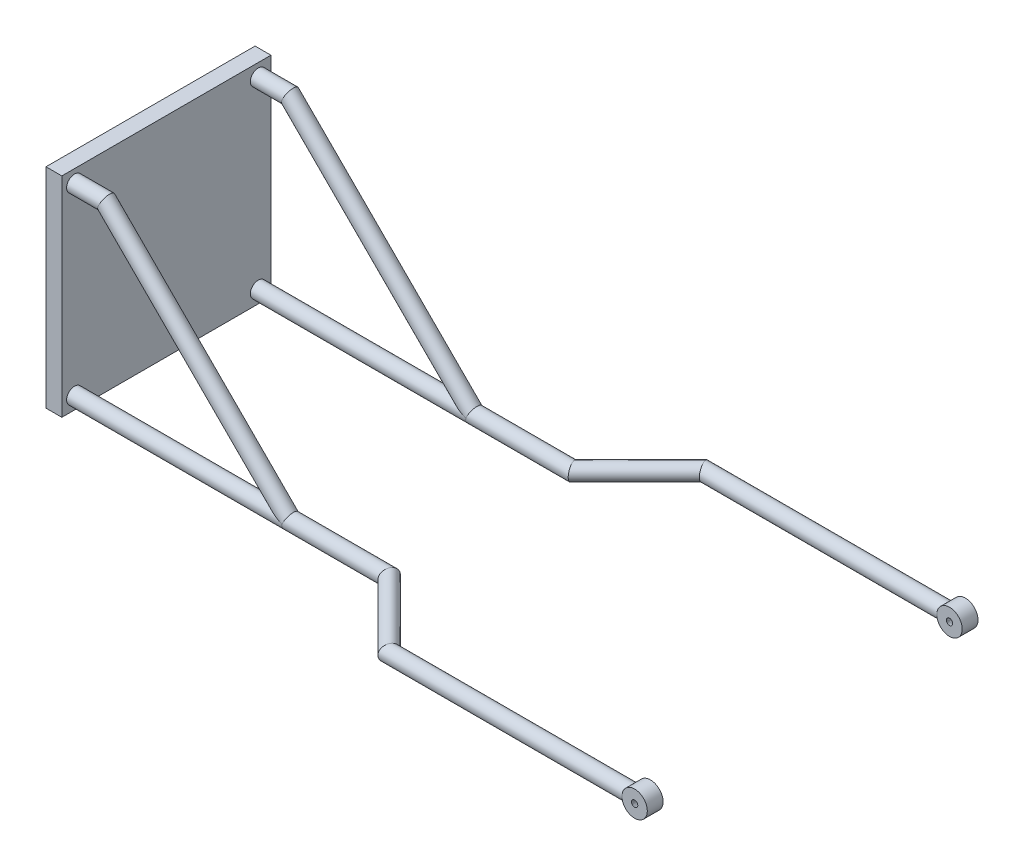
SolidWorks part; units mm, degrees
ref_plane "Plano frontal" through (0, 0, 0) normal (0, 0, 1) x (1, 0, 0)
ref_plane "Plano superior" through (0, 0, 0) normal (0, 1, 0) x (1, 0, 0)
ref_plane "Plano direito" through (0, 0, 0) normal (1, 0, 0) x (0, 0, -1)
sketch "Esboço1" plane through (0, 0, 0) normal (1, 0, 0) x (0, 0, -1)
  line L0 (-33, 33) -> (33, 33) construction
  line L1 (-33, 0) -> (33, 0)
  line L2 (-33, 0) -> (-33, 66)
  line L3 (-33, 66) -> (33, 66)
  line L4 (33, 0) -> (33, 66)
  line L5 (0, 0) -> (0, 66) construction
  circle A0 centre (-29, 62) radius 2.5
  circle A1 centre (-29, 4) radius 2.5
  circle A2 centre (29, 4) radius 2.5
  circle A3 centre (29, 62) radius 2.5
  point P11 (0, 0)
  dimension "D4" = 5
  dimension "D1" = 66
  dimension "D2" = 4
  dimension "D3" = 4
  dimension "D5" = 66
extrude "Ressalto-extrusão1" add sketch "Esboço1" along normal blind 5
ref_plane "Plano1" through (0, 0, 29) normal (0, 0, -1) x (-1, 0, 0)
sketch3d "3DSketch1"
  line L0 (0, 62, 29) -> (15, 62, 29)
  line L2 (5, 62, 29) -> (0, 62, 29) construction
  line L3 (73, 4, 29) -> (104.3, 4, 29)
  line L4 (73, 4, 29) -> (5, 4, 29) construction
  line L5 (5, 4, 29) -> (0, 4, 29) construction
  line L6 (15, 62, 29) -> (73, 4, 29)
  line L7 (104.3, 4, 29) -> (125, 4, 49.7)
  line L8 (125, 4, 49.7) -> (205, 4, 49.7)
  line L9 (104.3, 4, 29) -> (205, 4, 29) construction
  line L10 (205, 4, 29) -> (205, 4, 49.7) construction
  dimension "D1" = 20.7
  dimension "D4" = 135
  dimension "D2" = 15
  dimension "D3" = 45
  dimension "D5" = 200
  dimension "D6" = 80
sketch "Esboço3" plane through (0, 0, 0) normal (1, 0, 0) x (0, 0, -1)
  circle A0 centre (-29, 62) radius 2.5
  circle A1 centre (-29, 62) radius 2.5 construction
sweep "Varredura1" add profiles "Esboço3" path "3DSketch1"
sketch "Esboço5" plane through (0, 0, 0) normal (-1, 0, 0) x (0, 0, 1)
  circle A0 centre (29, 4) radius 2.5
  circle A1 centre (29, 4) radius 2.5 construction
sketch3d "3DSketch2"
  line L0 (0, 4, 29) -> (73, 4, 29)
sweep "Varredura2" add profiles "Esboço5" path "3DSketch2"
sketch "Esboço4" plane through (0, 0, 29) normal (0, 0, -1) x (-1, 0, 0)
  line L0 (-205, 6.5) -> (-205, 1.5) construction
  circle A0 centre (-205, 4) radius 4
  dimension "D1" = 8
extrude "Ressalto-extrusão2" add sketch "Esboço4" along normal mid plane 5 from offset 20.7 offset against normal yes
mirror "Espelhar1" about plane through (0, 0, 0) normal (0, 0, 1) of bodies 102 104 103
sketch "Esboço6" plane through (0, 0, 0) normal (0, 0, 1) x (1, 0, 0)
  circle A0 centre (205, 4) radius 1
  dimension "D1" = 2
extrude "Corte-extrusão1" cut sketch "Esboço6" against normal through all both and the other way through all
